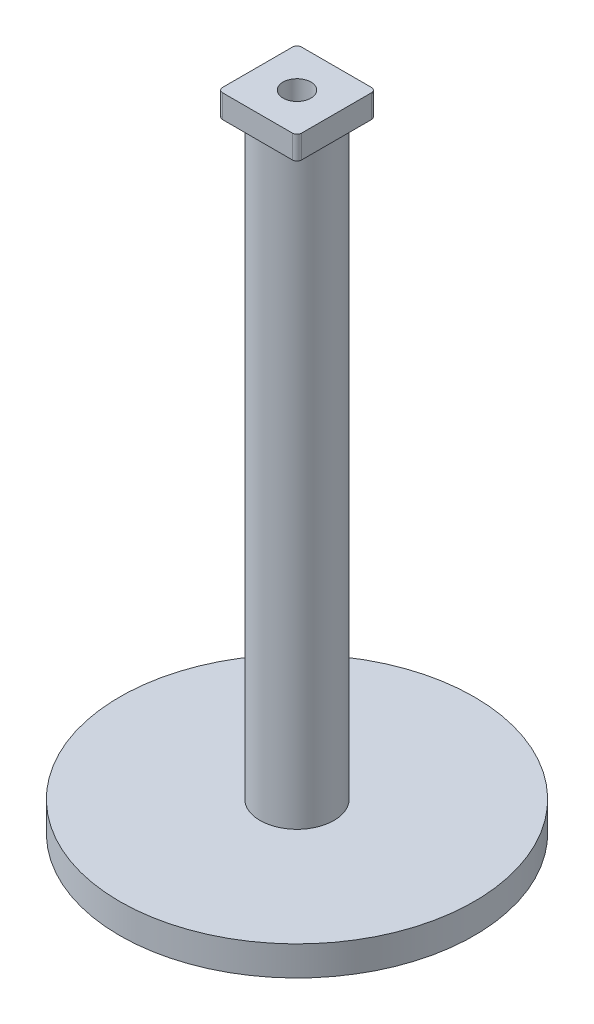
SolidWorks part; units mm, degrees
ref_plane "Front Plane" through (0, 0, 0) normal (0, 0, 1) x (1, 0, 0)
ref_plane "Top Plane" through (0, 0, 0) normal (0, 1, 0) x (1, 0, 0)
ref_plane "Right Plane" through (0, 0, 0) normal (1, 0, 0) x (0, 0, -1)
sketch "Sketch1" plane through (0, 0, 0) normal (0, 0, 1) x (1, 0, 0)
  line L0 (0, 131.177) -> (0, -23.3839) construction
  line L1 (0, 0) -> (38.1, 0)
  line L2 (38.1, 0) -> (38.1, 6.35)
  line L3 (38.1, 6.35) -> (7.9375, 6.35)
  line L4 (7.9375, 6.35) -> (7.9375, 133.35)
  line L8 (0, 133.35) -> (0, 0)
  line L9 (0, 133.35) -> (7.9375, 133.35)
  dimension "D1" = 76.2
  dimension "D2" = 6.35
  dimension "D3" = 15.875
  dimension "D4" = 127
revolve "Revolve1" add sketch "Sketch1" angle 360 about L0
sketch "Sketch2" plane through (0, 0, 0) normal (0, 1, 0) x (1, 0, 0)
  circle A0 centre (0, 0) radius 7.1438
  dimension "D1" = 14.2875
extrude "Cut-Extrude1" cut sketch "Sketch2" along normal offset from surface (120.65 mm away) 12.7 up to face at (0, 133.35, 7.9375)
sketch "Sketch5" plane through (0, 133.35, 0) normal (0, 1, 0) x (1, 0, 0)
  line L1 (-8.5, 8.5) -> (8.5, 8.5)
  line L2 (-8.5, 8.5) -> (-8.5, -8.5)
  line L3 (-8.5, -8.5) -> (8.5, -8.5)
  line L4 (8.5, 8.5) -> (8.5, -8.5)
  line L5 (-8.5, 8.5) -> (8.5, -8.5) construction
  line L6 (-8.5, -8.5) -> (8.5, 8.5) construction
  point P0 (0, 0)
  dimension "D1" = 17
  dimension "D2" = 17
extrude "Boss-Extrude3" add sketch "Sketch5" along normal blind 5
sketch "Sketch4" plane through (0, 138.35, 0) normal (0, 1, 0) x (1, 0, 0)
  circle A0 centre (0, 0) radius 3
  dimension "D1" = 6
extrude "Cut-Extrude2" cut sketch "Sketch4" against normal through all
fillet "Fillet1" radius 1 4 edges at (8.5, 135.85, 8.5) (-8.5, 135.85, 8.5) (8.5, 135.85, -8.5) (-8.5, 135.85, -8.5)
fillet "Fillet2" radius 0.25 1 edges at (0, 133.35, 7.9375)
